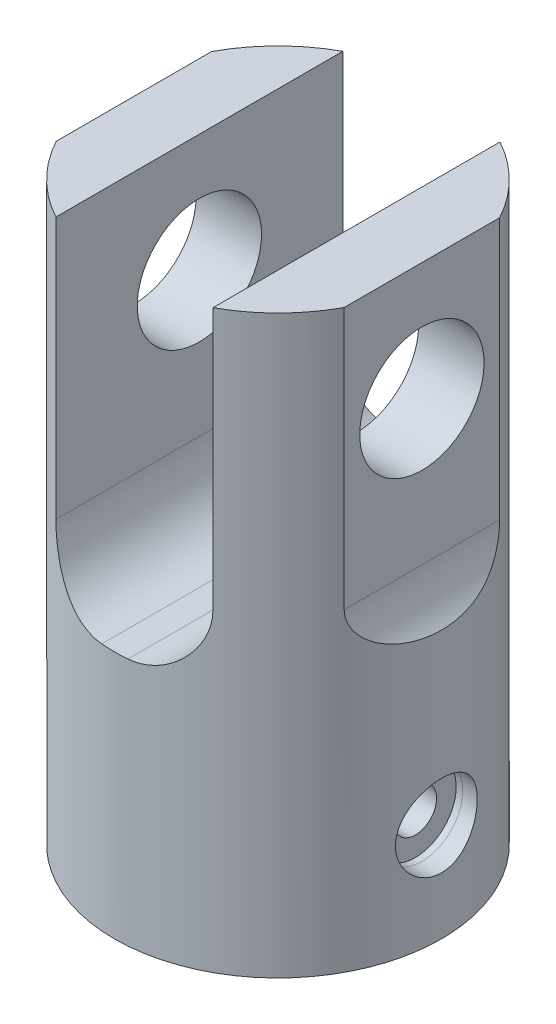
SolidWorks part; units mm, degrees
ref_plane "Front Plane" through (0, 0, 0) normal (0, 0, 1) x (1, 0, 0)
ref_plane "Top Plane" through (0, 0, 0) normal (0, 1, 0) x (1, 0, 0)
ref_plane "Right Plane" through (0, 0, 0) normal (1, 0, 0) x (0, 0, -1)
sketch "Sketch1" plane through (0, 0, 0) normal (0, 1, 0) x (1, 0, 0)
  circle A0 centre (0, 0) radius 15.5
  circle A1 centre (0, 0) radius 25
  dimension "D1" = 31
  dimension "D2" = 50
extrude "Boss-Extrude1" add sketch "Sketch1" along normal blind 30
sketch "Sketch3" plane through (0, 30, 0) normal (0, 1, 0) x (1, 0, 0)
  circle A0 centre (0, 0) radius 25 construction
  circle A1 centre (0, 0) radius 25
extrude "Boss-Extrude2" add sketch "Sketch3" along normal blind 8
sketch "Sketch4" plane through (0, 38, 0) normal (0, 1, 0) x (1, 0, 0)
  line L0 (-12, 21.9317) -> (-12, -21.9317)
  line L1 (0, 0) -> (0, 26.9876) construction
  line L2 (12, 21.9317) -> (12, -21.9317)
  line L3 (-22, 11.8743) -> (-22, -11.8743)
  line L4 (22, 11.8743) -> (22, -11.8743)
  circle A0 centre (0, 0) radius 25 construction
  circle A1 centre (0, 0) radius 25
  circle M4 centre (0, 0) radius 25
  dimension "D1" = 12
  dimension "D2" = 10
extrude "Boss-Extrude3" add sketch "Sketch4" along normal blind 50 contours L0 M4 | L2 M4 region at (-16.5471, 38, 0) region at (16.5471, 38, 0)
sketch "Sketch6" plane through (-22, 0, 0) normal (-1, 0, 0) x (0, 0, 1)
  line L5 (0, 88) -> (0, 0) construction
  line L6 (-11.8743, 88) -> (11.8743, 88) construction
  circle A0 centre (0, 70) radius 9.5
  dimension "D1" = 19
  dimension "D2" = 18
extrude "Cut-Extrude1" cut sketch "Sketch6" against normal through all and the other way through all
fillet "Fillet2" radius 10 4 edges at (22, 38, 0) (-22, 38, 0) (-12, 38, 0) (12, 38, 0)
sketch "Sketch7" plane through (-22, 0, 0) normal (-1, 0, 0) x (0, 0, 1)
  line L0 (0, 0) -> (0, 96.0435) construction
  line L1 (25, 0) -> (25, 38) construction
  line L2 (-25, 0) -> (25, 0) construction
  line L3 (-25, 0) -> (-25, 30) construction
  line L4 (-25, 30) -> (25, 30) construction
  line L5 (25, 0) -> (25, 30) construction
  circle A0 centre (0, 15) radius 8.25
  dimension "D2" = 16.5
  dimension "D1" = 30
  dimension "D3" = 15
extrude "Cut-Extrude2" cut sketch "Sketch7" along normal through all and the other way up to next
sketch "Sketch8" plane through (22, 0, 0) normal (1, 0, 0) x (0, 0, -1)
  line L0 (0, 0) -> (0, 72.105) construction
  circle A0 centre (0, 15) radius 6.25
  dimension "D1" = 12.5
  dimension "D2" = 15
extrude "Cut-Extrude3" cut sketch "Sketch8" along normal through all and the other way blind 1 draft 1
sketch "Sketch9" plane through (21, 0, 0) normal (1, 0, 0) x (0, 0, -1)
  circle A0 centre (0, 15) radius 3.25
  circle A1 centre (0, 15) radius 6.2325
  circle A2 centre (0, 15) radius 6.2325
  dimension "D2" = 6.5
  dimension "D1" = 0
extrude "Cut-Extrude4" cut sketch "Sketch9" against normal up to next contours A0
